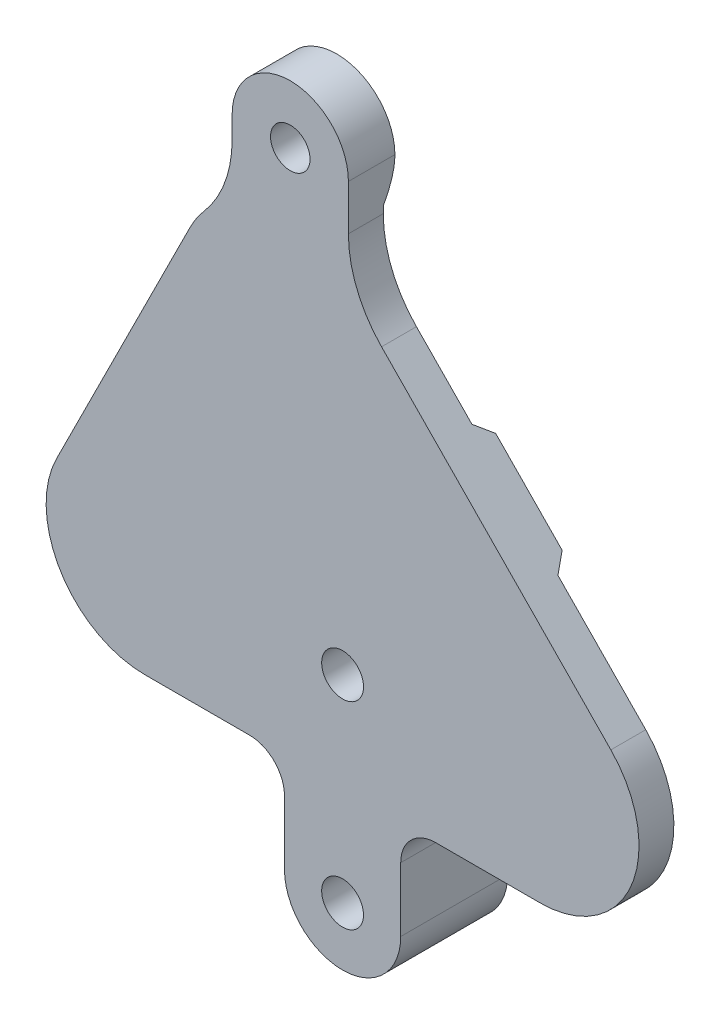
SolidWorks part; units mm, degrees
material "ABS"
ref_plane "Płaszczyzna przednia" through (0, 0, 0) normal (0, 0, 1) x (1, 0, 0)
ref_plane "Płaszczyzna górna" through (0, 0, 0) normal (0, 1, 0) x (1, 0, 0)
ref_plane "Płaszczyzna prawa" through (0, 0, 0) normal (1, 0, 0) x (0, 0, -1)
sketch "Szkic1" plane through (0, 0, 0) normal (0, 0, 1) x (1, 0, 0)
  line L0 (-7.6026, 3.8013) -> (3.8974, 26.8013)
  line L1 (17.5761, 28.944) -> (40.0761, 5.944)
  line L2 (34, -8.5) -> (25, -8.5)
  line L3 (22, -17) -> (22, -11.5)
  line L4 (12, -17) -> (12, -11.5)
  line L5 (9, -8.5) -> (0, -8.5)
  arc A0 (-7.6026, 3.8013) -> (0, -8.5) centre (0, 0) ccw
  arc A1 (17.5761, 28.944) -> (3.8974, 26.8013) centre (11.5, 23) ccw
  arc A2 (34, -8.5) -> (40.0761, 5.944) centre (34, 0) ccw
  circle A3 centre (17, 0) radius 1.8
  circle A4 centre (17, -17) radius 1.8
  arc A5 (12, -17) -> (22, -17) centre (17, -17) ccw
  arc A6 (12, -11.5) -> (9, -8.5) centre (9, -11.5) ccw
  arc A7 (22, -11.5) -> (25, -8.5) centre (25, -11.5) cw
  point P20 (12, -8.5)
  dimension "D1" = 17
  dimension "D2" = 17
  dimension "D3" = 3.6
  dimension "D4" = 34
  dimension "D5" = 17
  dimension "D6" = 23
  dimension "D7" = 17
  dimension "D8" = 11.5
  dimension "D10" = 23
  dimension "D11" = 17
  dimension "D12" = 3.6
  dimension "D14" = 5
  dimension "D15" = 3
  dimension "D9" = 23
  dimension "D13" = 17
extrude "Dodanie-wyciągnięcie1" add sketch "Szkic1" along normal blind 3
sketch "Szkic2" plane through (0, 0, 0) normal (0, 0, -1) x (-1, 0, 0)
  circle A0 centre (-34, 0) radius 6
  circle A1 centre (-11.5, 23) radius 6
  circle A2 centre (0, 0) radius 6
  dimension "D1" = 12
  dimension "D2" = 12
  dimension "D3" = 12
extrude "Wytnij-wyciągnięcie1" cut sketch "Szkic2" against normal blind 2
chamfer "Sfazowanie1" distance 0.5 angle 45 3 edges at (5.5, 23, 2) (-6, 0, 2) (28, 0, 2)
sketch "Szkic3" plane through (0, 0, 0) normal (0, 0, -1) x (-1, 0, 0)
  line L2 (-22, -17) -> (-22, 3.786)
  line L3 (-22.9021, 5.9305) -> (-31.6846, 14.522)
  line L4 (-25.9676, 20.366) -> (-16.0643, 10.678)
  line L5 (-40.0761, 5.944) -> (-17.5761, 28.944) construction
  line L6 (1.022, 16.9626) -> (-12.6248, 10.1392)
  line L7 (-3.8974, 26.8013) -> (7.6026, 3.8013) construction
  line L8 (2.6833, 13.64) -> (-10.3416, 7.1276)
  line L9 (-12, -17) -> (-12, 4.4443)
  line L10 (1.022, 16.9626) -> (2.6833, 13.64)
  line L11 (-25.9676, 20.366) -> (-31.6846, 14.522)
  arc A0 (-22, -17) -> (-12, -17) centre (-17, -17) ccw
  circle A2 centre (-17, 0) radius 1.8
  circle A3 centre (-17, -17) radius 1.8
  circle A4 centre (-34, 0) radius 5.5 construction
  circle A5 centre (-11.5, 23) radius 5.5 construction
  circle A6 centre (0, 0) radius 5.5 construction
  arc A7 (-10.3416, 7.1276) -> (-12, 4.4443) centre (-9, 4.4443) ccw
  arc A8 (-12.6248, 10.1392) -> (-16.0643, 10.678) centre (-13.9665, 12.8225) cw
  arc A9 (-22, 3.786) -> (-22.9021, 5.9305) centre (-25, 3.786) ccw
  dimension "D1" = 10
  dimension "D3" = 12
  dimension "D2" = 12
  dimension "D4" = 11
  dimension "D9" = 3
  dimension "D5" = 11
  dimension "D6" = 90
  dimension "D7" = 90
  dimension "D8" = 90
extrude "Dodanie-wyciągnięcie2" add sketch "Szkic3" along normal blind 1.2
chamfer "Sfazowanie2" distance 1.2 angle 45 9 edges at (12, -3.5279, 0) (22, -3.857, 0) (27.2933, 10.2262, 0) (22.2347, 4.9492, 0) (5.8014, 13.5509, 0) (14.4307, 9.8586, 0) (21.016, 15.522, 0) (3.8292, 10.3838, 0) (11.552, 6.0215, 0)
sketch "Szkic4" plane through (0, 0, -1.2) normal (0, 0, -1) x (-1, 0, 0)
  line L0 (-22, -12.1) -> (-12, -12.1)
  line L1 (-22, -12.1) -> (-22, -17)
  line L3 (-12, -12.1) -> (-12, -17)
  arc A0 (-22, -17) -> (-12, -17) centre (-17, -17) ccw
  circle A1 centre (-17, -17) radius 1.8
  dimension "D1" = 10
  dimension "D2" = 4.9
  dimension "D3" = 10
extrude "Dodanie-wyciągnięcie3" add sketch "Szkic4" along normal blind 5
sketch "Szkic5" plane through (0, 0, 3) normal (0, 0, 1) x (1, 0, 0)
  line L0 (7.5, 37) -> (7.5, 30.5)
  line L1 (17.5, 37) -> (17.5, 29.0208)
  line L2 (40.0761, 5.944) -> (17.5761, 28.944) construction
  line L3 (3.8974, 26.8013) -> (-7.6026, 3.8013) construction
  line L4 (40.0761, 5.944) -> (17.5761, 28.944)
  line L5 (3.8974, 26.8013) -> (-7.6026, 3.8013)
  circle A0 centre (12.5, 37) radius 1.7
  circle A1 centre (17, 0) radius 1.8 construction
  arc A2 (17.5, 37) -> (7.5, 37) centre (12.5, 37) ccw
  arc A3 (17.5761, 28.944) -> (3.8974, 26.8013) centre (11.5, 23) ccw construction
  arc A4 (17.5761, 28.944) -> (3.8974, 26.8013) centre (11.5, 23) ccw
  arc M11 (17.5761, 28.944) -> (3.8974, 26.8013) centre (11.5, 23) ccw
  dimension "D1" = 4.5
  dimension "D2" = 37
  dimension "D3" = 3.4
  dimension "D4" = 10
extrude "Dodanie-wyciągnięcie4" add sketch "Szkic5" against normal blind 3 contours L1 A2 L0 A0 M11 region at (12.5, 41.8362, 3)
sketch "Szkic6" plane through (0, 0, 0) normal (0, 0, -1) x (-1, 0, 0)
  line L6 (-13.1615, 11.2125) -> (0.4853, 18.0359)
  line L7 (0.4853, 18.0359) -> (-3.8974, 26.8013)
  line L8 (-7.5, 30.5) -> (-7.5, 37)
  line L9 (-17.5, 37) -> (-17.5, 29.0208)
  line L10 (-17.5761, 28.944) -> (-25.1285, 21.2238)
  line L11 (-25.1285, 21.2238) -> (-15.2252, 11.5358)
  line L12 (-13.1615, 11.2125) -> (0.4853, 18.0359)
  line L13 (0.4853, 18.0359) -> (-3.8974, 26.8013)
  line L14 (-7.5, 30.5) -> (-7.5, 37)
  line L15 (-17.5, 37) -> (-17.5, 29.0208)
  line L16 (-17.5761, 28.944) -> (-25.1285, 21.2238)
  line L17 (-25.1285, 21.2238) -> (-15.2252, 11.5358)
  circle A0 centre (-12.5, 37) radius 1.7 construction
  circle A1 centre (-12.5, 37) radius 1.7
  circle A2 centre (-12.5, 37) radius 5
  arc A4 (-15.2252, 11.5358) -> (-13.1615, 11.2125) centre (-13.9665, 12.8225) ccw
  arc A5 (-3.8974, 26.8013) -> (-7.5, 30.5) centre (-11.5, 23) ccw
  arc A6 (-7.5, 37) -> (-17.5, 37) centre (-12.5, 37) ccw
  arc A7 (-17.5, 29.0208) -> (-17.5761, 28.944) centre (-11.5, 23) ccw
  arc A8 (-15.2252, 11.5358) -> (-13.1615, 11.2125) centre (-13.9665, 12.8225) ccw
  arc A9 (-3.8974, 26.8013) -> (-7.5, 30.5) centre (-11.5, 23) ccw
  arc A10 (-7.5, 37) -> (-17.5, 37) centre (-12.5, 37) ccw
  arc A11 (-17.5, 29.0208) -> (-17.5761, 28.944) centre (-11.5, 23) ccw
  arc M17 (-7.5, 37) -> (-17.5, 37) centre (-12.5, 37) ccw
  circle M22 centre (-12.5, 37) radius 1.7
  dimension "D1" = 0
extrude "Dodanie-wyciągnięcie5" add sketch "Szkic6" along normal blind 1 contours A2 M17 M22 region at (12.5, 32.1414, 0)
chamfer "Sfazowanie3" distance 1 angle 45 1 edges at (12.5, 32, 0)
fillet "Zaokrąglenie1" radius 10 2 edges at (17.5, 29.0208, 1.5) (7.5, 30.5, 1.5)
